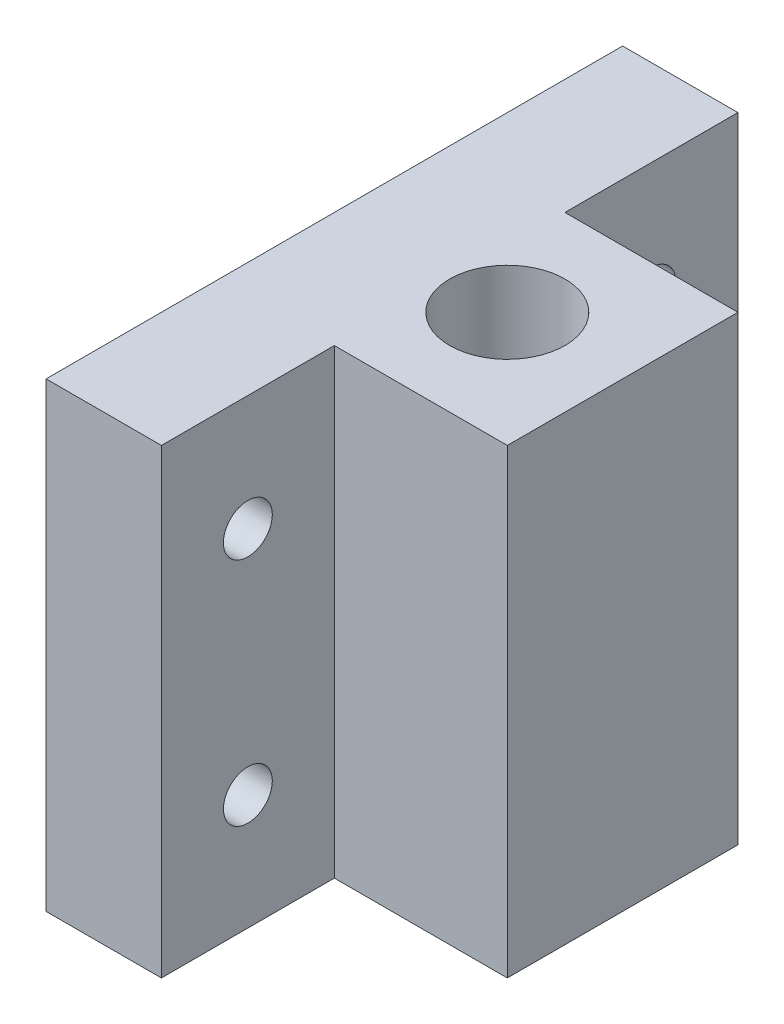
SolidWorks part; units mm, degrees
ref_plane "Front Plane" through (0, 0, 0) normal (0, 0, 1) x (1, 0, 0)
ref_plane "Top Plane" through (0, 0, 0) normal (0, 1, 0) x (1, 0, 0)
ref_plane "Right Plane" through (0, 0, 0) normal (1, 0, 0) x (0, 0, -1)
sketch "Sketch1" plane through (0, 0, 0) normal (0, 1, 0) x (1, 0, 0)
  line L1 (0, 20) -> (50, 20)
  line L2 (0, 20) -> (0, -20)
  line L3 (0, -20) -> (50, -20)
  line L4 (50, 20) -> (50, -20)
  point P0 (0, 0)
  dimension "D1" = 50
  dimension "D2" = 40
extrude "Boss-Extrude1" add sketch "Sketch1" along normal blind 80
sketch "Sketch4" plane through (0, 0, 0) normal (-1, 0, 0) x (0, 0, 1)
  line L0 (-20, 80) -> (20, 80) construction
  line L1 (-50, 80) -> (50, 80)
  line L2 (-50, 80) -> (-50, 0)
  line L3 (-50, 0) -> (50, 0)
  line L4 (50, 80) -> (50, 0)
  line L5 (-50, 80) -> (50, 0) construction
  line L6 (-50, 0) -> (50, 80) construction
  line L7 (55, 0) -> (-55, 0) construction
  line L8 (0, 80) -> (0, 0) construction
  line L9 (-20, 0) -> (20, 0) construction
  point P0 (0, 40)
  dimension "D1" = 100
extrude "Boss-Extrude2" add sketch "Sketch4" against normal blind 20
sketch "Sketch5" plane through (20, 0, 0) normal (1, 0, 0) x (0, 0, -1)
  line L0 (-35, 80) -> (-35, 0) construction
  line L1 (-50, 80) -> (-20, 80) construction
  line L2 (-20, 0) -> (-50, 0) construction
  circle A0 centre (-35, 20) radius 4.24
  circle A1 centre (-35, 60) radius 4.24
  dimension "D1" = 8.48
  dimension "D2" = 40
  dimension "D3" = 8.48
  dimension "D4" = 20
extrude "screw hole" cut sketch "Sketch5" against normal through all
mirror "Mirror1" about plane through (0, 0, 0) normal (0, 0, 1) of "screw hole"
sketch "Sketch6" plane through (0, 80, 0) normal (0, 1, 0) x (1, 0, 0)
  line L0 (0, 0) -> (50, 0) construction
  line L1 (0, 50) -> (0, -50) construction
  line L2 (50, -20) -> (50, 20) construction
  circle A0 centre (30, 0) radius 8
  dimension "D1" = 16
  dimension "D2" = 30
extrude "rod hole" cut sketch "Sketch6" against normal through all
sketch "Sketch7" plane through (0, 80, 0) normal (0, 1, 0) x (1, 0, 0)
  circle A0 centre (30, 0) radius 10
  dimension "D1" = 20
extrude "Cut-Extrude5" cut sketch "Sketch7" against normal blind 50
chamfer "Chamfer2" distance 2 angle 45 1 edges at (30, 30, 8)
sketch "Sketch8" plane through (50, 0, 0) normal (1, 0, 0) x (0, 0, -1)
  line L0 (0, 80) -> (0, 0)
  line L1 (-20, 80) -> (20, 80) construction
  line L2 (-20, 0) -> (20, 0) construction
sketch "Sketch9" plane through (0, 0, 50) normal (0, 0, 1) x (1, 0, 0)
  line L0 (0, 80) -> (15, 90)
  line L1 (15, 90) -> (15, 80)
  line L2 (15, 80) -> (0, 80)
  line L3 (20, 80) -> (0, 80) construction
  dimension "D1" = 10
  dimension "D2" = 15
extrude "guide" [suppressed] add sketch "Sketch9" against normal up to surface (100 mm away)
fillet "Fillet1" [suppressed] radius 2
fillet "Fillet2" [suppressed] radius 10
